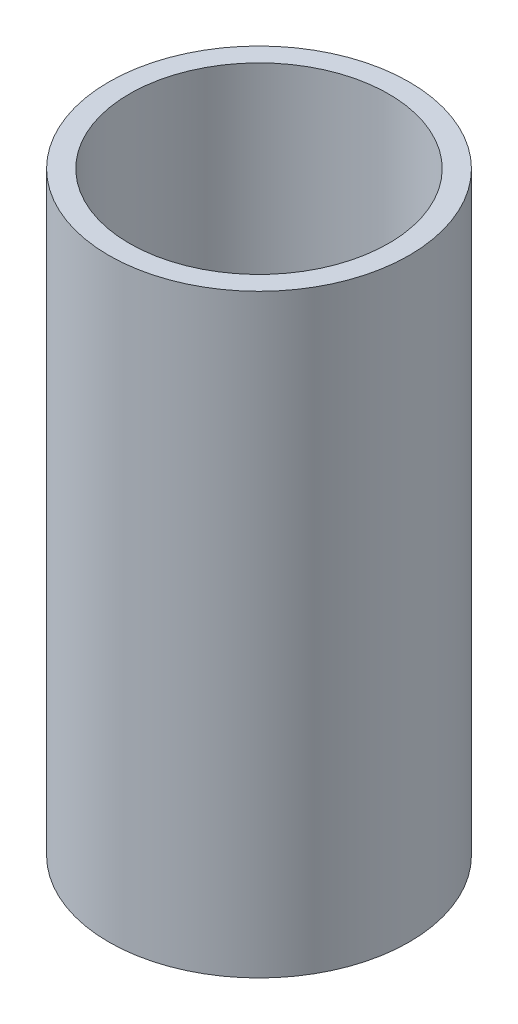
SolidWorks part; units mm, degrees
ref_plane "Front Plane" through (0, 0, 0) normal (0, 0, 1) x (1, 0, 0)
ref_plane "Top Plane" through (0, 0, 0) normal (0, 1, 0) x (1, 0, 0)
ref_plane "Right Plane" through (0, 0, 0) normal (1, 0, 0) x (0, 0, -1)
sketch "Sketch1" plane through (0, 0, 0) normal (0, 1, 0) x (1, 0, 0)
  circle A0 centre (0, 0) radius 42.5
  dimension "SLEEVE_OD" = 85
extrude "Boss-Extrude1" add sketch "Sketch1" along normal blind 168.2374
sketch "Sketch2" plane through (0, 0, 0) normal (0, 1, 0) x (1, 0, 0)
  circle A0 centre (0, 0) radius 36.6584
  dimension "BORE_D" = 73.3168
extrude "Cut-Extrude1" cut sketch "Sketch2" along normal through all
chamfer "Chamfer1" distance 2.8946 angle 60 rebuild error yes
